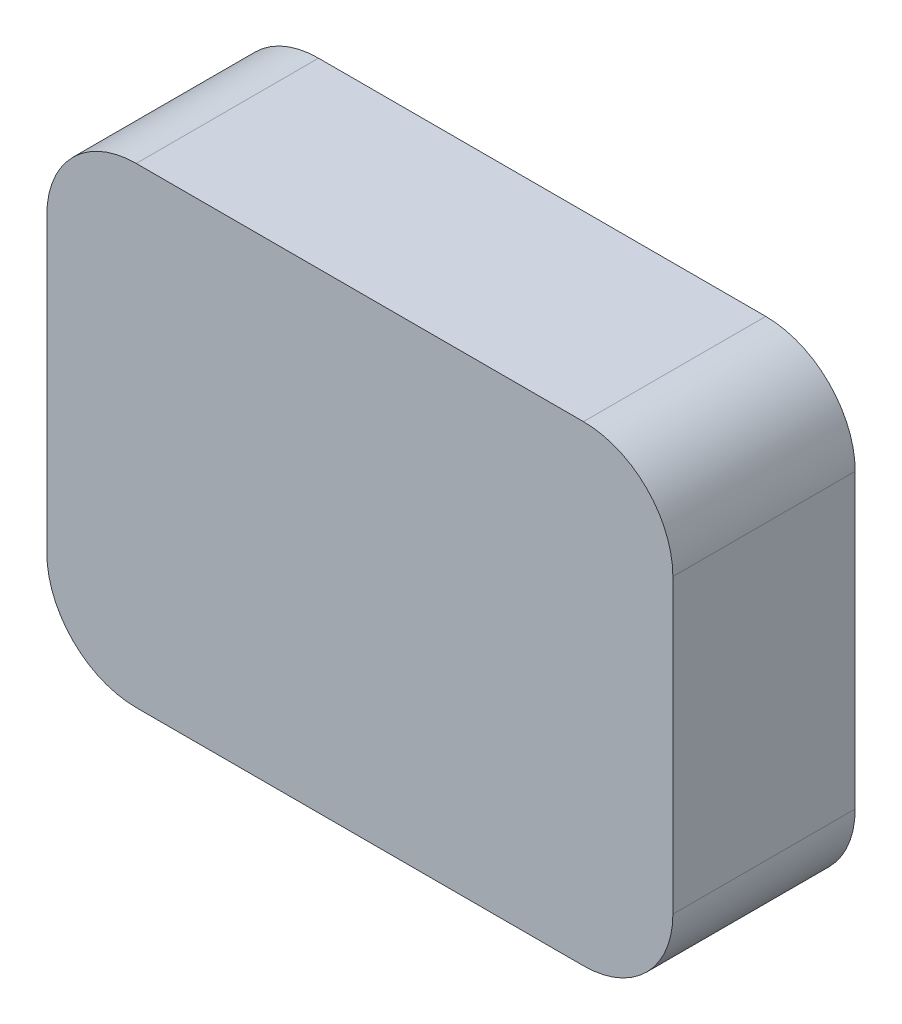
SolidWorks part; units mm, degrees
ref_plane "Plan de face" through (0, 0, 0) normal (0, 0, 1) x (1, 0, 0)
ref_plane "Plan de dessus" through (0, 0, 0) normal (0, 1, 0) x (1, 0, 0)
ref_plane "Plan de droite" through (0, 0, 0) normal (1, 0, 0) x (0, 0, -1)
sketch "Esquisse1" plane through (0, 0, 0) normal (0, 0, 1) x (1, 0, 0)
  line L1 (-26, 27) -> (26, 27)
  line L2 (-36, 17) -> (-36, -17)
  line L3 (-26, -27) -> (26, -27)
  line L4 (36, 17) -> (36, -17)
  line L5 (-36, 27) -> (36, -27) construction
  line L6 (-36, -27) -> (36, 27) construction
  arc A0 (-36, -17) -> (-26, -27) centre (-26, -17) ccw
  arc A1 (26, -27) -> (36, -17) centre (26, -17) ccw
  arc A2 (26, 27) -> (36, 17) centre (26, 17) cw
  arc A3 (-26, 27) -> (-36, 17) centre (-26, 17) ccw
  point P0 (0, 0)
  dimension "D1" = 10
  dimension "D2" = 52
  dimension "D3" = 34
sketch "profil" plane through (0, 0, 0) normal (1, 0, 0) x (0, 0, -1)
  line L0 (0, -25.5219) -> (4.1106, -25.5219)
  line L1 (4.1106, -25.5219) -> (10, -21)
  line L3 (10, -27) -> (0, -27)
  line L4 (0, -27) -> (0, -25.5219)
  line L6 (0, -17) -> (0, -27) construction
  line L7 (0, -27) -> (0, 27) construction
  line L10 (10, -21) -> (10, -27) construction
  line L11 (10, -24) -> (12.7162, -24) construction
  line L12 (10, -25.7405) -> (10, -27) construction
  line L15 (10, -27) -> (10, -26.6)
  line L16 (10, -26.6) -> (9.8, -26.6)
  line L17 (9.8, -26.6) -> (9.8, -25.8)
  line L18 (9.8, -25.8) -> (10, -25.8)
  line L20 (10, -25.8) -> (10, -25.4)
  line L21 (10, -21) -> (10, -21.4)
  line L22 (10, -21.4) -> (9.8, -21.4)
  line L23 (9.8, -21.4) -> (9.8, -22.2)
  line L24 (9.8, -22.2) -> (10, -22.2)
  line L25 (10, -22.2) -> (10, -22.6)
  line L39 (10, -22.6) -> (10.4, -22.6)
  line L54 (10.4, -22.6) -> (10.4, -23)
  line L55 (10.4, -23) -> (10.8, -23)
  line L56 (10.8, -23) -> (10.8, -23.4)
  line L57 (10.8, -23.4) -> (11.2, -23.4)
  line L58 (11.2, -23.4) -> (11.2, -23.8)
  line L59 (11.2, -23.8) -> (11.6, -23.8)
  line L60 (11.6, -23.8) -> (11.6, -24.2)
  line L61 (11.6, -24.2) -> (11.2, -24.2)
  line L62 (11.2, -24.2) -> (11.2, -24.6)
  line L63 (11.2, -24.6) -> (10.8, -24.6)
  line L64 (10.8, -24.6) -> (10.8, -25)
  line L65 (10.8, -25) -> (10.4, -25)
  line L66 (10.4, -25) -> (10.4, -25.4)
  line L67 (10.4, -25.4) -> (10, -25.4)
  dimension "D3" = 10
  dimension "D4" = 6
  dimension "D5" = 0.8
  dimension "D7" = 0.4
  dimension "D1" = 0.4
  dimension "D8" = 0.4
sweep "Balayage1" add profiles "profil" path "Esquisse1"
extrude "Boss.-Extru.1" add sketch "Esquisse1<3>" along normal blind 1.2
sketch "Esquisse1<3>" plane through (0, 0, 0) normal (0, 0, 1) x (1, 0, 0) same geometry as "Esquisse1"
fillet "Congé1" radius 2 9 edges at (-32.0259, 23.0259, 0) (-34.5219, 0, 0) (-32.0259, -23.0259, 0) (-13, -25.5219, 0) (13, -25.5219, 0) (32.0259, -23.0259, 0) (34.5219, 0, 0) (32.0259, 23.0259, 0) (0, 25.5219, 0)
sketch "Esquisse2" plane through (0, 0, 0) normal (0, 0, 1) x (1, 0, 0)
  line L8 (36.4, -17) -> (36.4, 17)
  line L9 (-26, -27.4) -> (26, -27.4)
  line L10 (-36.4, 17) -> (-36.4, -17)
  line L11 (26, 27.4) -> (-26, 27.4)
  line L12 (36.4, -17) -> (36.4, 17)
  line L13 (-26, -27.4) -> (26, -27.4)
  line L14 (-36.4, 17) -> (-36.4, -17)
  line L15 (26, 27.4) -> (-26, 27.4)
  arc A8 (36.4, 17) -> (26, 27.4) centre (26, 17) ccw
  arc A9 (26, -27.4) -> (36.4, -17) centre (26, -17) ccw
  arc A10 (-36.4, -17) -> (-26, -27.4) centre (-26, -17) ccw
  arc A11 (-26, 27.4) -> (-36.4, 17) centre (-26, 17) ccw
  arc A12 (36.4, 17) -> (26, 27.4) centre (26, 17) ccw
  arc A13 (26, -27.4) -> (36.4, -17) centre (26, -17) ccw
  arc A14 (-36.4, -17) -> (-26, -27.4) centre (-26, -17) ccw
  arc A15 (-26, 27.4) -> (-36.4, 17) centre (-26, 17) ccw
  dimension "D1" = 0.4
extrude "Extru.-Mince1" add sketch "Esquisse2" against normal blind 20 and the other way up to surface (1.2 mm away) thin other way up to face at (0, 0, 1.2) thin type one direction reverse wall 0.4
equation "\"buse\"=0.4"
equation "\"coque\"= \"buse\" * 4"
equation "\"diam_silicone\"=3"
equation "\"couche\"=0.2"
equation "\"D1@Boss.-Extru.1\"=\"fond\""
equation "\"fond\"= \"couche\" * 6"
equation "\"D2@Esquisse1\"=\"dim_ext_L@boitier_balaye-1.Part\""
equation "\"D4@profil\"=\"epaisseur_jonction@boitier_balaye-1.Part\""
equation "\"D3@Esquisse1\"=\"dim_ext@boitier_balaye-1.Part\""
equation "\"D8@profil\"=\"couche\"*2"
